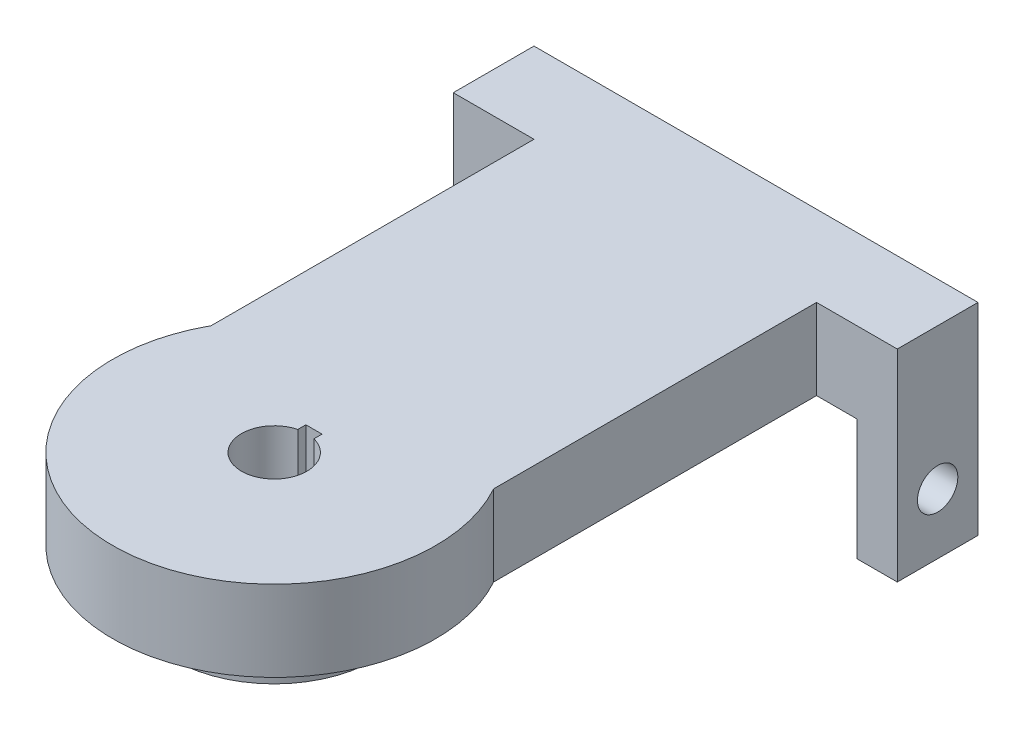
SolidWorks part; units mm, degrees
ref_plane "Front Plane" through (0, 0, 0) normal (0, 0, 1) x (1, 0, 0)
ref_plane "Top Plane" through (0, 0, 0) normal (0, 1, 0) x (1, 0, 0)
ref_plane "Right Plane" through (0, 0, 0) normal (1, 0, 0) x (0, 0, -1)
sketch "Sketch1" plane through (0, 0, 0) normal (0, 1, 0) x (1, 0, 0)
  circle A21 centre (0, 0) radius 20
  dimension "D1" = 40
extrude "Boss-Extrude1" add sketch "Sketch1" along normal blind 10
sketch "Sketch2" plane through (0, 10, 0) normal (0, 1, 0) x (1, 0, 0)
  line L0 (-1, 4.9246) -> (-1, 3.9246)
  line L1 (-1, 4.9246) -> (1, 4.9246)
  line L2 (1, 4.9246) -> (1, 3.9246)
  arc A0 (-1, 3.9246) -> (1, 3.9246) centre (0, 0) ccw
  point P5 (0, 4.9246)
  dimension "D1" = 8.1
  dimension "D2" = 1
  dimension "D3" = 2
extrude "Cut-Extrude1" cut sketch "Sketch2" against normal through all
sketch "Sketch3" plane through (0, 0, 0) normal (0, 1, 0) x (1, 0, 0)
  line L0 (-17.5, 59.6825) -> (-17.5, 9.6825)
  line L1 (-17.5, 59.6825) -> (17.5, 59.6825)
  line L2 (17.5, 59.6825) -> (17.5, 9.6825)
  circle A0 centre (0, 0) radius 20 construction
  arc A1 (17.5, 9.6825) -> (-17.5, 9.6825) centre (0, 0) ccw
  point P6 (0, 59.6825)
  dimension "D1" = 35
  dimension "D2" = 50
extrude "Boss-Extrude2" add sketch "Sketch3" along normal up to surface (10 mm away) up to face at (0, 10, -2.431)
sketch "Sketch5" plane through (0, 0, 0) normal (0, -1, 0) x (1, 0, 0)
  line L0 (-1, -3.9246) -> (-1, -4.9246)
  line L1 (-1, -4.9246) -> (1, -4.9246)
  line L2 (1, -4.9246) -> (1, -3.9246)
  circle A0 centre (0, 0) radius 12.5
  arc A1 (1, -3.9246) -> (-1, -3.9246) centre (0, 0) ccw
  dimension "D1" = 25
extrude "Boss-Extrude3" add sketch "Sketch5" along normal blind 6
sketch "Sketch6" plane through (0, 0, -59.6825) normal (0, 0, -1) x (-1, 0, 0)
  line L0 (-27.5, 10) -> (27.5, 10)
  line L1 (-27.5, 10) -> (-27.5, -15)
  line L2 (-27.5, -15) -> (-22.5, -15)
  line L3 (-22.5, -15) -> (-22.5, 0)
  line L4 (-22.5, 0) -> (22.5, 0)
  line L5 (22.5, 0) -> (22.5, -15)
  line L6 (22.5, -15) -> (27.5, -15)
  line L7 (27.5, -15) -> (27.5, 10)
  line L8 (-17.5, 10) -> (17.5, 10) construction
  line L9 (-17.5, 0) -> (17.5, 0) construction
  point P5 (28.4942, 0)
  point P10 (0, 0)
  dimension "D1" = 45
  dimension "D2" = 5
  dimension "D3" = 15
extrude "Boss-Extrude4" add sketch "Sketch6" against normal blind 10
sketch "Sketch7" plane through (27.5, 0, 0) normal (1, 0, 0) x (0, 0, -1)
  line L0 (49.6825, -15) -> (59.6825, -15) construction
  line L1 (9.6825, 0) -> (49.6825, 0) construction
  circle A0 centre (54.6825, -7.5) radius 2.5
  point P4 (54.6825, -15)
  dimension "D2" = 5
  dimension "D1" = 7.5
extrude "Cut-Extrude2" cut sketch "Sketch7" against normal through all
